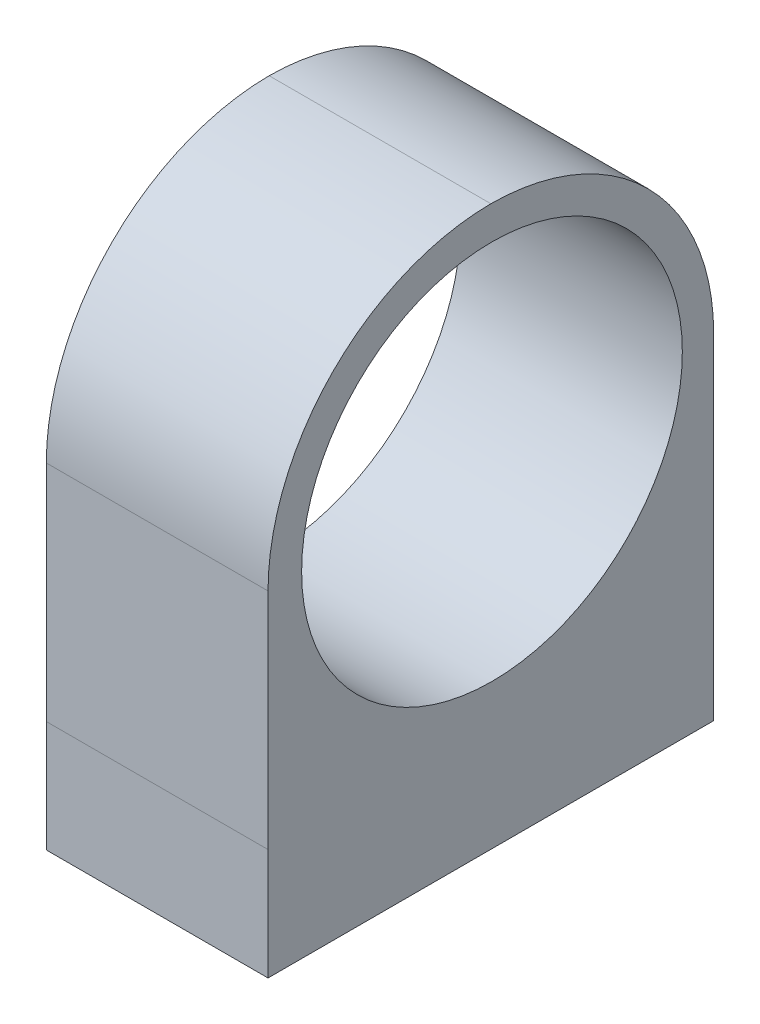
SolidWorks part; units mm, degrees
ref_plane "Front Plane" through (0, 0, 0) normal (0, 0, 1) x (1, 0, 0)
ref_plane "Top Plane" through (0, 0, 0) normal (0, 1, 0) x (1, 0, 0)
ref_plane "Right Plane" through (0, 0, 0) normal (1, 0, 0) x (0, 0, -1)
sketch "Sketch1" plane through (0, 0, 0) normal (0, 1, 0) x (1, 0, 0)
  line L1 (49.5, -99.5) -> (-49.5, -99.5)
  line L2 (49.5, -99.5) -> (49.5, 99.5)
  line L3 (49.5, 99.5) -> (-49.5, 99.5)
  line L4 (-49.5, -99.5) -> (-49.5, 99.5)
  line L5 (49.5, -99.5) -> (-49.5, 99.5) construction
  line L6 (49.5, 99.5) -> (-49.5, -99.5) construction
  point P0 (0, 0)
extrude "Boss-Extrude1" add sketch "Sketch1" along normal blind 49.6724
sketch "Sketch2" plane through (0, 49.6724, 0) normal (0, 1, 0) x (1, 0, 0)
  line L0 (-49.5, 99.5) -> (-49.5, -99.5) construction
  line L1 (49.5, -99.4978) -> (-49.5, -99.4978)
  line L2 (49.5, -99.4978) -> (49.5, 99.4978)
  line L3 (49.5, 99.4978) -> (-49.5, 99.4978)
  line L4 (-49.5, -99.4978) -> (-49.5, 99.4978)
  line L5 (49.5, -99.4978) -> (-49.5, 99.4978) construction
  line L6 (49.5, 99.4978) -> (-49.5, -99.4978) construction
  point P0 (0, 0)
extrude "Boss-Extrude2" add sketch "Sketch2" along normal blind 200
fillet "Fillet1" radius 100 2 edges at (0, 249.6724, -99.4978) (0, 249.6724, 99.4978)
sketch "Sketch3" plane through (49.5, 0, 0) normal (1, 0, 0) x (0, 0, -1)
  circle A0 centre (0.5022, 149.6724) radius 85
extrude "Cut-Extrude1" cut sketch "Sketch3" against normal blind 99
